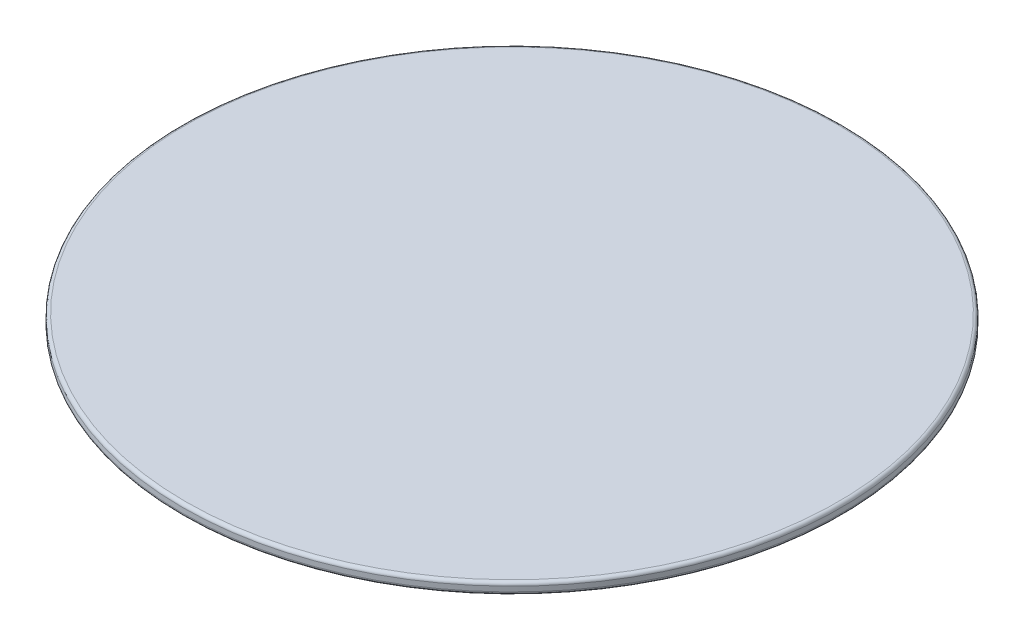
SolidWorks part; units mm, degrees
ref_plane "Front Plane" through (0, 0, 0) normal (0, 0, 1) x (1, 0, 0)
ref_plane "Top Plane" through (0, 0, 0) normal (0, 1, 0) x (1, 0, 0)
ref_plane "Right Plane" through (0, 0, 0) normal (1, 0, 0) x (0, 0, -1)
sketch "Sketch1" plane through (0, 0, 0) normal (0, 1, 0) x (1, 0, 0)
  circle A0 centre (0, 0) radius 100
  dimension "D1" = 200
extrude "Boss-Extrude1" add sketch "Sketch1" along normal blind 10
chamfer "Chamfer3" distance 12 angle 30 1 edges at (0, 0, 100)
sketch "Sketch7" plane through (0, 0, 0) normal (0, -1, 0) x (-1, 0, 0)
  circle A0 centre (0, 0) radius 35
  dimension "D1" = 70
extrude "Boss-Extrude5" add sketch "Sketch7" along normal blind 10
fillet "Fillet2" radius 1 2 edges at (0, 6.9282, 100) (0, 10, 100)
sketch "Sketch2" plane through (0, -10, 0) normal (0, -1, 0) x (1, 0, 0)
  circle A0 centre (0, 0) radius 30.5
  circle A1 centre (0, 0) radius 19.5
  dimension "D1" = 61
  dimension "D2" = 39
extrude "Cut-Extrude1" cut sketch "Sketch2" against normal blind 1
sketch "Sketch3" plane through (0, -10, 0) normal (0, -1, 0) x (-1, 0, 0)
  line L1 (1, -31.01) -> (-1, -31.01)
  line L2 (1, -31.01) -> (1, -29.99)
  line L3 (1, -29.99) -> (-1, -29.99)
  line L4 (-1, -31.01) -> (-1, -29.99)
  line L5 (1, -31.01) -> (-1, -29.99) construction
  line L6 (1, -29.99) -> (-1, -31.01) construction
  line L7 (1, -20.01) -> (-1, -20.01)
  line L8 (1, -20.01) -> (1, -18.99)
  line L9 (1, -18.99) -> (-1, -18.99)
  line L10 (-1, -20.01) -> (-1, -18.99)
  line L11 (1, -20.01) -> (-1, -18.99) construction
  line L12 (1, -18.99) -> (-1, -20.01) construction
  circle A0 centre (0, 0) radius 30.5 construction
  circle A1 centre (0, 0) radius 30.5 construction
  circle A2 centre (0, 0) radius 19.5 construction
  point P0 (0, -30.5)
  point P9 (0, -19.5)
  dimension "D1" = 2
  dimension "D2" = 1.02
  dimension "D3" = 1.02
  dimension "D4" = 2
extrude "Boss-Extrude2" add sketch "Sketch3" against normal blind 1
fillet "Fillet1" radius 1 4 edges at (-1, -9.5, 20.01) (1, -9.5, 20.01) (-1, -9.5, 29.99) (1, -9.5, 29.99)
pattern_circular "CirPattern1" count 8 over 360 about axis through (0, 0, 0) along (0, 1, 0) of "Boss-Extrude2", "Fillet1"
sketch "Sketch4" plane through (0, -10, 0) normal (0, -1, 0) x (1, 0, 0)
  circle A0 centre (0, 0) radius 8
  dimension "D1" = 16
extrude "Boss-Extrude3" add sketch "Sketch4" along normal blind 7
sketch "Sketch8" plane through (0, -17, 0) normal (0, -1, 0) x (1, 0, 0)
  circle A0 centre (0, 0) radius 4.5
  dimension "D1" = 9
extrude "Cut-Extrude3" cut sketch "Sketch8" against normal blind 22
chamfer "Chamfer2" distance 2 angle 45 1 edges at (0, -17, -4.5)
sketch "Sketch5" plane through (0, -17, 0) normal (0, -1, 0) x (-1, 0, 0)
  line L1 (-1.6, -5.4) -> (1.6, -5.4)
  line L2 (-1.6, -5.4) -> (-1.6, -3.8381)
  line L3 (-1.6, -3.8381) -> (1.6, -3.8381)
  line L4 (1.6, -5.4) -> (1.6, -3.8381)
  point P0 (0, -3.8381)
  dimension "D1" = 3.2
  dimension "D2" = 5.4
extrude "Cut-Extrude2" cut sketch "Sketch5" against normal up to surface (22 mm away) up to face at (0, 5, -4.5)
sketch "Sketch6" plane through (0, 5, 0) normal (0, -1, 0) x (-1, 0, 0)
  line L1 (0.85, 5.8799) -> (-0.85, 5.8799)
  line L2 (0.85, 5.8799) -> (0.85, 4)
  line L3 (0.85, 4) -> (-0.85, 4)
  line L4 (-0.85, 5.8799) -> (-0.85, 4)
  point P4 (0, 4)
  dimension "D1" = 1.7
  dimension "D2" = 4
extrude "Boss-Extrude4" add sketch "Sketch6" along normal up to vertex (20 mm away)
chamfer "Chamfer4" distance 2 distance2 0.4 1 edges at (0, -15, -4)
fillet "Fillet3" radius 1 2 edges at (-0.85, -4, -4) (0.85, -4, -4)
pattern_circular "CirPattern2" count 5 over 360 about axis through (0, 0, 0) along (0, 1, 0) of "Boss-Extrude4", "Chamfer4", "Fillet3"
